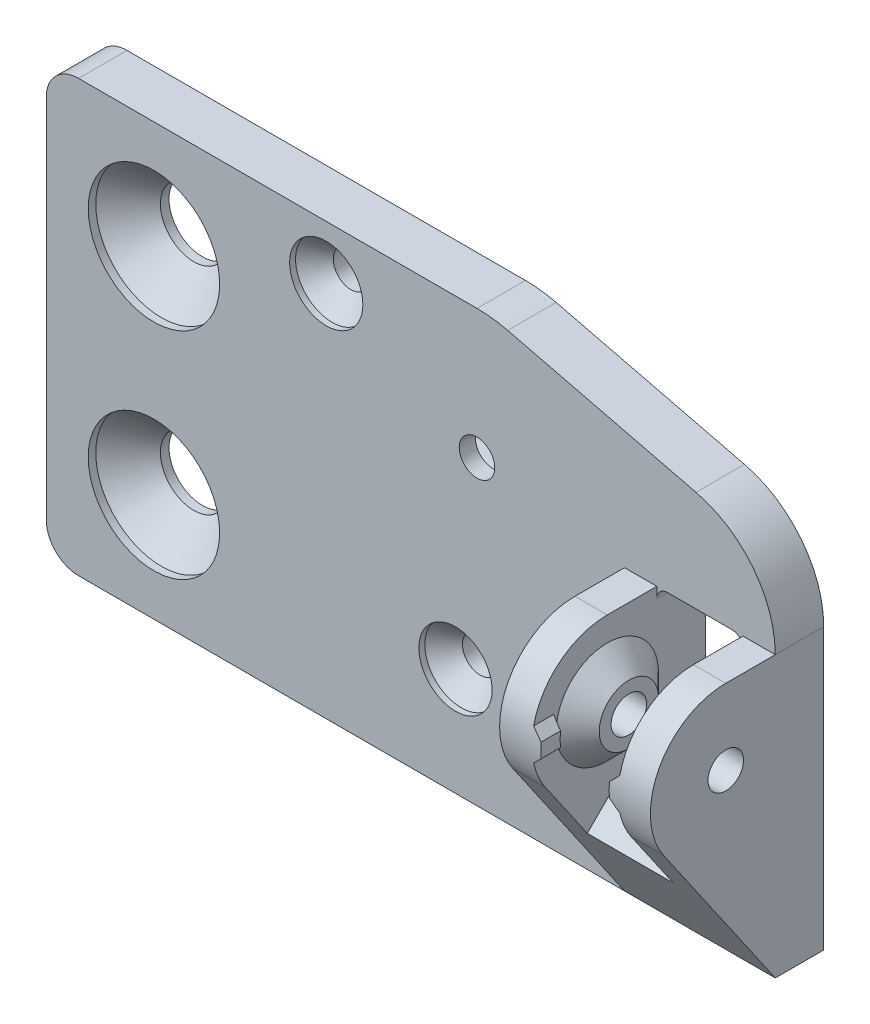
SolidWorks part; units mm, degrees
material "Custom Plastic"
ref_plane "Front Plane" through (0, 0, 0) normal (0, 0, 1) x (1, 0, 0)
ref_plane "Top Plane" through (0, 0, 0) normal (0, 1, 0) x (1, 0, 0)
ref_plane "Right Plane" through (0, 0, 0) normal (1, 0, 0) x (0, 0, -1)
sketch "Sketch1" plane through (0, 0, 0) normal (0, 0, 1) x (1, 0, 0)
  line L0 (-10, -20) -> (-10, 0) construction
  line L1 (-10, -20) -> (10, -20) construction
  line L2 (-10, 0) -> (10, 0) construction
  line L3 (10, -20) -> (10, 0) construction
  line L4 (-10, -20) -> (10, 0) construction
  line L5 (-10, 0) -> (10, -20) construction
  line L6 (-10, 0) -> (-10, 20) construction
  line L7 (-10, 17) -> (-10, -17)
  line L8 (-10, 20) -> (10, 20) construction
  line L9 (10, 0) -> (10, 20) construction
  line L10 (-10, 0) -> (10, 20) construction
  line L11 (-10, 20) -> (10, 0) construction
  line L12 (-7, 20) -> (10, 20)
  line L13 (57.7, 20) -> (57.7, -20)
  line L15 (10, 20) -> (57.7, 20)
  line L18 (57.7, -20) -> (-7, -20)
  circle A0 centre (0, 10) radius 3.1
  circle A1 centre (0, -10) radius 3.1
  arc A2 (-7, 20) -> (-10, 17) centre (-7, 17) ccw
  arc A3 (-10, -17) -> (-7, -20) centre (-7, -17) ccw
  circle A4 centre (30, 8) radius 1.65
  point P0 (0, 10)
  point P1 (0, -10)
  dimension "D2" = 6.2
  dimension "D6" = 3
  dimension "D4" = 3.3
  dimension "D1" = 20
  dimension "D3" = 57.7
  dimension "D5" = 20
  dimension "D7" = 8
extrude "Boss-Extrude1" add sketch "Sketch1" along normal blind 4.5
sketch "Sketch2" plane through (0, -20, 0) normal (0, -1, 0) x (1, 0, 0)
  line L0 (10, 0) -> (10, -16)
  line L2 (10, -16) -> (19, -16)
  line L3 (19, -16) -> (57.7, 0)
  line L4 (57.7, 0) -> (10, 0)
  dimension "D1" = 16
  dimension "D2" = 10
  dimension "D3" = 9
extrude "Boss-Extrude2" add sketch "Sketch2" against normal blind 15
sketch "Sketch3" plane through (57.7, 0, 0) normal (1, 0, 0) x (0, 0, -1)
  line L0 (-9.1, 6) -> (-4.5, 6)
  line L1 (-4.5, -20) -> (-14.8625, -4.9741)
  line L2 (-4.5, 6) -> (-4.5, -20)
  line L3 (-4.5, -20) -> (-4.5, 20) construction
  arc A0 (-9.1, 6) -> (-14.8625, -4.9741) centre (-9.1, -1) ccw
  dimension "D1" = 7
  dimension "D2" = 1
  dimension "D3" = 4.6
extrude "Boss-Extrude3" add sketch "Sketch3" against normal blind 14
sketch "Sketch4" plane through (0, -5, 0) normal (0, 1, 0) x (1, 0, 0)
  line L1 (10, 0) -> (57.7, 0)
  line L2 (10, 0) -> (10, 5.1)
  line L3 (10, 5.1) -> (19, 5.1)
  line L4 (57.7, 0) -> (57.7, 16)
  line L5 (19, 16) -> (19, 5.1)
  line L6 (19, 16) -> (57.7, 16)
  line L7 (57.7, 0) -> (10, 0) construction
  line L8 (10, 0) -> (10, 16) construction
  dimension "D1" = 5.1
extrude "Cut-Extrude1" cut sketch "Sketch4" against normal offset from surface (11 mm away) 4 contours L6 L4 L1 L2 L3 L5 up to face at (17.9063, -20, -1.3125)
sketch "Sketch5" plane through (57.7, 0, 0) normal (1, 0, 0) x (0, 0, -1)
  circle A0 centre (-9.1, -1) radius 1.65
  dimension "D1" = 3.3
extrude "Cut-Extrude2" cut sketch "Sketch5" against normal through all
sketch "Sketch6" plane through (57.7, 0, 0) normal (1, 0, 0) x (0, 0, -1)
  line L0 (-5.2109, -4.8891) -> (-19.2142, -18.8924)
  line L1 (-19.2142, -18.8924) -> (-19.2142, 16.8924)
  line L2 (-19.2142, 16.8924) -> (-5.2109, 2.8891)
  arc A0 (-5.2109, -4.8891) -> (-5.2109, 2.8891) centre (-9.1, -1) ccw
  dimension "D1" = 5.5
extrude "Cut-Extrude3" cut sketch "Sketch6" against normal blind 8 from offset 3 offset against normal yes
fillet "Fillet1" radius 5 1 edges at (14.5, -5, -16)
sketch "Sketch7" plane through (19, 0, 0) normal (1, 0, 0) x (0, 0, -1)
  line L2 (16, -20) -> (0, -20) construction
  line L3 (16, -16) -> (16, -20) construction
  circle A0 centre (11, -10) radius 2.1
  dimension "D1" = 4.2
  dimension "D2" = 10
  dimension "D3" = 5
extrude "Cut-Extrude4" cut sketch "Sketch7" against normal through all
sketch "Sketch8" plane through (19, 0, 0) normal (1, 0, 0) x (0, 0, -1)
  circle A0 centre (11, -10) radius 4.1
  dimension "D1" = 8.2
extrude "Cut-Extrude5" cut sketch "Sketch8" against normal offset from surface (1.5 mm away) 7.5 up to face at (10, -12.1, -11)
chamfer "Chamfer1" distance 2 angle 45 1 edges at (17.5, -12.1, -11)
ref_axis "Axis1" through (54.7, -1, 9.1) along (1, 0, 0)
sketch "Sketch9" plane through (0, 0, 0) normal (0, 0, 1) x (1, 0, 0)
  line L0 (46.7, -4.8891) -> (46.7, 2.8891) construction
  line L1 (46.7, 6) -> (54.7, 6)
  line L2 (46.7, 6) -> (46.7, 3.5)
  line L3 (46.7, 3.5) -> (54.7, 3.5) construction
  line L4 (54.7, 6) -> (54.7, 3.5)
  line L5 (54.7, 2.8891) -> (54.7, -4.8891) construction
  line L6 (54.7, 2.8891) -> (54.7, 6) construction
  line L7 (46.7, -5.5) -> (54.7, -5.5) construction
  line L8 (46.7, -5.5) -> (46.7, -8)
  line L9 (46.7, -8) -> (54.7, -8)
  line L10 (54.7, -5.5) -> (54.7, -8)
  line L11 (54.7, 3.5) -> (54.7, -5.5)
  line L12 (54.7, -1) -> (57.7, -1) construction
  line L13 (46.7, 3.5) -> (46.7, -5.5)
  point P14 (54.7, -1)
  dimension "D1" = 2.5
  dimension "D2" = 9
extrude "Cut-Extrude6" cut sketch "Sketch9" along normal through all
sketch "Sketch10" plane through (0, 0, 0) normal (0, 0, -1) x (-1, 0, 0)
  line L1 (-57.7, 6) -> (-57.7, 20)
  line L2 (-57.7, 20) -> (-30, 20)
  line L3 (-50.34, 15.3777) -> (-32.8517, 19.6562)
  arc A0 (-30, 20) -> (-32.8517, 19.6562) centre (-30, 8) ccw
  arc A1 (-50.34, 15.3777) -> (-57.7, 6) centre (-48.0457, 6) ccw
extrude "Cut-Extrude7" cut sketch "Sketch10" against normal through all
sketch "Sketch11" plane through (0, 0, 0) normal (0, 0, -1) x (-1, 0, 0)
  line L1 (-30.75, -8.4123) -> (-30.75, -11.5877) construction
  line L2 (-30.75, -11.5877) -> (-28, -13.1754) construction
  line L3 (-28, -13.1754) -> (-25.25, -11.5877) construction
  line L4 (-25.25, -11.5877) -> (-25.25, -8.4123) construction
  line L5 (-25.25, -8.4123) -> (-28, -6.8246) construction
  line L6 (-28, -6.8246) -> (-30.75, -8.4123) construction
  line L7 (-13.25, 13.4123) -> (-13.25, 16.5877) construction
  line L8 (-13.25, 16.5877) -> (-16, 18.1754) construction
  line L9 (-16, 18.1754) -> (-18.75, 16.5877) construction
  line L10 (-18.75, 16.5877) -> (-18.75, 13.4123) construction
  line L11 (-18.75, 13.4123) -> (-16, 11.8246) construction
  line L12 (-16, 11.8246) -> (-13.25, 13.4123) construction
  circle A0 centre (-16, 15) radius 1.65
  circle A1 centre (-28, -10) radius 1.65
  circle A2 centre (-28, -10) radius 2.75 construction
  circle A3 centre (-16, 15) radius 2.75 construction
  circle A4 centre (-30, 8) radius 1.65 construction
  point P20 (-30, 8)
  dimension "D1" = 3.3
  dimension "D2" = 5.5
  dimension "D5" = 2
  dimension "D6" = 10
  dimension "D3" = 14
  dimension "D4" = 15
extrude "Cut-Extrude9" cut sketch "Sketch11" against normal through all
sketch "Sketch13" plane through (46.7, 0, 0) normal (1, 0, 0) x (0, 0, -1)
  circle A0 centre (-9.1, -1) radius 2.75
  circle A1 centre (-9.1, -1) radius 1.65
  circle A4 centre (-9.1, -1) radius 1.65 construction
  point P9 (4.6036, -2.5)
  point P11 (10.6036, -2.5)
  point P12 (4.6036, 0.5)
  point P13 (10.6036, 0.5)
  dimension "D1" = 5.5
extrude "Boss-Extrude4" add sketch "Sketch13" along normal blind 2
sketch "Sketch15" plane through (46.7, 0, 0) normal (1, 0, 0) x (0, 0, -1)
  line L0 (-14.079, 0.5) -> (-15.9374, 0.5)
  line L2 (-14.079, -2.5) -> (-15.9374, -2.5)
  arc A1 (-15.9374, 0.5) -> (-15.9374, -2.5) centre (-9.1, -1) ccw
  arc A2 (-9.1, 6) -> (-14.8625, -4.9741) centre (-9.1, -1) ccw construction
  arc A3 (-9.1, 6) -> (-14.8625, -4.9741) centre (-9.1, -1) ccw construction
  arc A4 (-14.079, 0.5) -> (-14.079, -2.5) centre (-9.1, -1) ccw
  dimension "D4" = 5.2
  dimension "D3" = 3
extrude "Boss-Extrude5" add sketch "Sketch15" along normal blind 0.825
ref_plane "Plane1" through (50.7, 0, 0) normal (1, 0, 0) x (0, 0, -1)
mirror "Mirror1" about plane through (50.7, 0, 0) normal (1, 0, 0) of "Boss-Extrude5", "Boss-Extrude4"
chamfer "Chamfer3" distance 2 angle 45 2 edges at (54.7, 1.75, 9.1) (46.7, 1.75, 9.1)
sketch "Sketch14" plane through (0, 0, 4.5) normal (0, 0, -1) x (-1, 0, 0)
  circle A0 centre (0, -10) radius 6.1
  circle A1 centre (0, 10) radius 6.1
  dimension "D1" = 12.2
extrude "Cut-Extrude10" cut sketch "Sketch14" along normal blind 0.7
chamfer "Chamfer4" distance 3 angle 45 2 edges at (-3.1, -10, 3.8) (-3.1, 10, 3.8)
chamfer "Chamfer5" distance 0.83 angle 45 4 edges at (53.875, -2.5, 15.0082) (53.875, 0.5, 15.0082) (47.525, -2.5, 15.0082) (47.525, 0.5, 15.0082)
sketch "Sketch16" plane through (0, 0, 4.5) normal (0, 0, -1) x (-1, 0, 0)
  circle A0 centre (-28, -10) radius 3.4
  circle A1 centre (-16, 15) radius 3.4
  dimension "D1" = 6.8
extrude "Cut-Extrude11" cut sketch "Sketch16" along normal blind 0.5
chamfer "Chamfer6" distance 1.8 angle 45 2 edges at (26.35, -10, 4) (14.35, 15, 4)
sketch "Sketch17" plane through (10, 0, 0) normal (-1, 0, 0) x (0, 0, 1)
  line L0 (-11, -10) -> (-9.5151, -8.5151)
  line L1 (-9.5151, -8.5151) -> (-10.5502, -7.48)
  line L2 (-10.5502, -7.48) -> (-11.4498, -7.48)
  line L3 (-11.4498, -7.48) -> (-12.4849, -8.5151)
  line L4 (-12.4849, -8.5151) -> (-11, -10)
  circle A0 centre (-11, -10) radius 2.1 construction
  point P0 (-11, -7.9)
  dimension "D1" = 0.42
extrude "Cut-Extrude12" cut sketch "Sketch17" against normal through all
sketch "Sketch18" plane through (0, 0, 0) normal (0, 0, -1) x (-1, 0, 0)
  circle A0 centre (-30, 8) radius 6.25
  dimension "D1" = 12.5
extrude "Cut-Extrude13" cut sketch "Sketch18" against normal blind 3
fillet "Fillet2" radius 1 2 edges at (46.7, 6, 2.25) (54.7, 6, 2.25)
equation "\"y-cross-rib-thickness\"=6"
equation "\"y-rib-thickness\"=6"
equation "\"bed-plate-thickness\"=6"
equation "\"x-plate-thickness\"=5"
equation "\"rod-diameter\"=12"
equation "\"t-nut-hole-diameter\"=3"
equation "\"y-plate-thickness\"=5"
equation "\"D1@Sketch4\"=\"y-plate-thickness\"+.1"
equation "\"D1@Boss-Extrude5\"=(8-6.35)/2"
equation "\"enclosure-thickness\"=0.6"
equation "\"M3-Clearance\"=3.3"
equation "\"M4-Clearance\"=4.3"
equation "\"M5-Clearance\"=5.3"
equation "\"M6-Clearance\"=6.3"
equation "\"M8-Clearance\"=8.3"
equation "\"623-Bearing-Dia\"=11.2"
